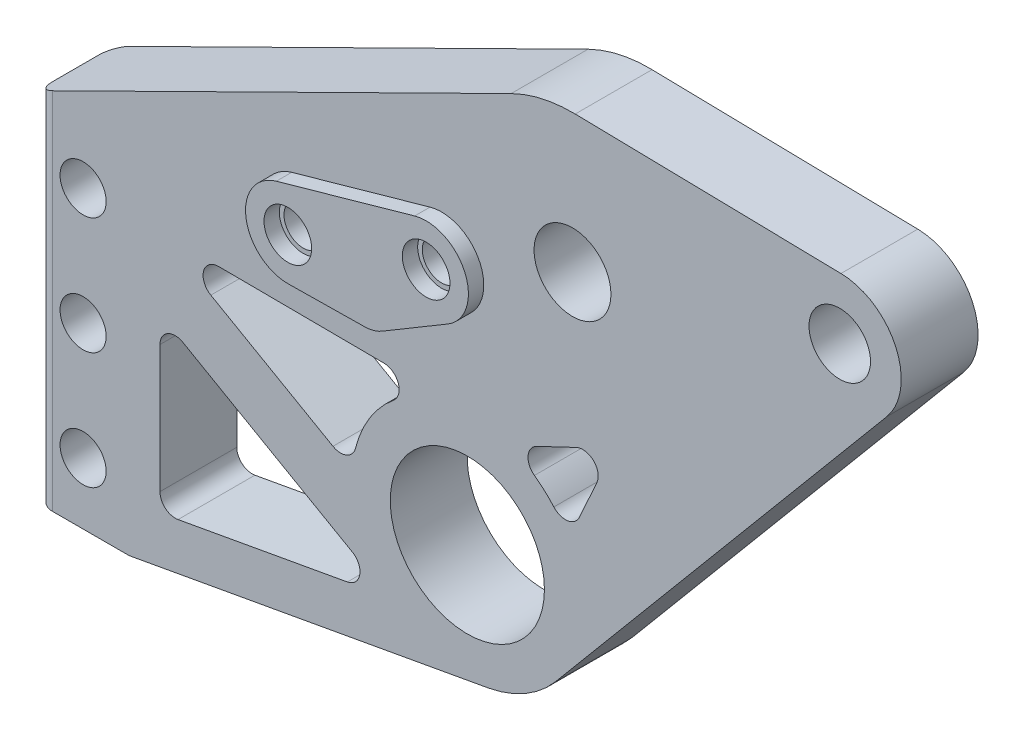
SolidWorks part; units mm, degrees
ref_plane "前视基准面" through (0, 0, 0) normal (0, 0, 1) x (1, 0, 0)
ref_plane "上视基准面" through (0, 0, 0) normal (0, 1, 0) x (1, 0, 0)
ref_plane "右视基准面" through (0, 0, 0) normal (1, 0, 0) x (0, 0, -1)
sketch "草图1" plane through (0, 0, 0) normal (0, 0, 1) x (1, 0, 0)
  line L0 (0, 0) -> (0, 23.2)
  line L1 (3, 11.6) -> (28, 11.6) construction
  line L2 (3, 11.6) -> (0, 11.6) construction
  line L3 (3, 19.2) -> (3, 4) construction
  line L4 (0, 0) -> (6, 0)
  line L5 (28, 11.6) -> (34.8404, 30.3939) construction
  line L6 (28, 11.6) -> (22.2988, 23.804) construction
  line L7 (0, 23.2) -> (30.8499, 38.4608)
  line L8 (6, 0) -> (29.3346, 4.2197)
  line L9 (34.8355, 8.5135) -> (43.043, 26.69)
  line L10 (22.2988, 23.804) -> (21.818, 25.5074) construction
  line L11 (17.3188, 24.2376) -> (26.3173, 26.7773) construction
  circle A0 centre (3, 19.2) radius 1.5
  circle A1 centre (3, 11.6) radius 1.5
  circle A2 centre (3, 4) radius 1.5
  circle A3 centre (28, 11.6) radius 5.015
  circle A4 centre (34.8404, 30.3939) radius 2.5
  arc A5 (43.043, 26.69) -> (30.8499, 38.4608) centre (34.8404, 30.3939) ccw
  circle A6 centre (22.2988, 23.804) radius 1.515
  arc A7 (29.3346, 4.2197) -> (34.8355, 8.5135) centre (28, 11.6) ccw
  circle A8 centre (17.3188, 24.2376) radius 1.25
  circle A9 centre (26.3173, 26.7773) radius 1.25
  point P26 (21.818, 25.5074)
  dimension "D2" = 25
  dimension "D3" = 3
  dimension "D4" = 7.6
  dimension "D6" = 4
  dimension "D7" = 10.03
  dimension "D10" = 5
  dimension "D11" = 18
  dimension "D14" = 3.03
  dimension "D15" = 15
  dimension "D18" = 2.5
  dimension "D1" = 3
  dimension "D5" = 6
  dimension "D8" = 70
  dimension "D9" = 20
  dimension "D12" = 64.96
  dimension "D13" = 13.47
  dimension "D16" = 1.77
  dimension "D17" = 9.35
  dimension "D19" = 15.761
extrude "凸台-拉伸1" add sketch "草图1" along normal blind 5
fillet "圆角1" radius 1 2 edges at (0, 11.6, 0) (0, 11.6, 5)
sketch "草图2" plane through (0, 0, 5) normal (0, 0, 1) x (1, 0, 0)
  line L0 (16.5719, 26.8842) -> (25.5703, 29.4239)
  line L1 (17.3561, 21.4879) -> (22.3293, 21.5553)
  line L2 (23.4484, 21.8712) -> (27.7231, 24.4137)
  arc A0 (16.5719, 26.8842) -> (17.3561, 21.4879) centre (17.3188, 24.2376) ccw
  arc A1 (27.7231, 24.4137) -> (25.5703, 29.4239) centre (26.3173, 26.7773) ccw
  arc A2 (22.3293, 21.5553) -> (23.4484, 21.8712) centre (22.2988, 23.804) ccw
  circle A3 centre (17.3188, 24.2376) radius 1.55
  circle A4 centre (26.3173, 26.7773) radius 1.55
  dimension "D1" = 5.5
  dimension "D2" = 3.1
  dimension "D3" = 3.1
extrude "凸台-拉伸2" add sketch "草图2" along normal blind 1 separate body
sketch "草图3" plane through (0, 0, 5) normal (0, 0, 1) x (1, 0, 0)
  line L0 (6, 0) -> (6, 26.1681) construction
  line L1 (30.8499, 38.4608) -> (1, 23.6947) construction
  line L2 (8, 0.3617) -> (8, 27.1574) construction
  line L3 (37.5481, 21.8108) -> (34.5705, 15.2165)
  line L4 (6, 0) -> (29.3346, 4.2197) construction
  line L5 (8, 3.4103) -> (22.8965, 6.1041)
  line L6 (8, 14.6181) -> (22.8965, 6.1041)
  line L7 (8, 14.6181) -> (8, 3.4103)
  line L8 (8, 19.2253) -> (20.5149, 12.0726)
  line L9 (8, 19.2253) -> (28.0469, 19.0999)
  line L10 (34.8355, 8.5135) -> (43.043, 26.69) construction
  line L11 (30.749, 18.578) -> (37.5481, 21.8108)
  line L12 (26.1673, 32.7974) -> (18.6487, 16.1466) construction
  line L13 (18.6487, 16.1466) -> (31.2532, 22.1396) construction
  circle A0 centre (28, 11.6) radius 7.5 construction
  arc A1 (20.5149, 12.0726) -> (28.0469, 19.0999) centre (28, 11.6) cw
  circle A2 centre (34.8404, 30.3939) radius 9 construction
  arc A3 (34.5705, 15.2165) -> (30.749, 18.578) centre (28, 11.6) ccw
  arc A4 (26.1673, 32.7974) -> (31.2532, 22.1396) centre (34.8404, 30.3939) ccw construction
  dimension "D1" = 15
  dimension "D6" = 18
  dimension "D2" = 2
  dimension "D3" = 3
  dimension "D4" = 40
  dimension "D5" = 4
  dimension "D7" = 3
  dimension "D8" = 3
  dimension "D9" = 3
extrude "切除-拉伸1" cut sketch "草图3" against normal blind 10 contours A3 L3 L11 | L8 A1 L9 | L6 L7 L5 | A4 L12 L13
fillet "圆角2" radius 1 9 edges at (22.8965, 6.1041, 2.5) (8, 3.4103, 2.5) (30.749, 18.578, 2.5) (37.5481, 21.8108, 2.5) (34.5705, 15.2165, 2.5) (8, 14.6181, 2.5) (28.0469, 19.0999, 2.5) (20.5149, 12.0726, 2.5) (8, 19.2253, 2.5)
sketch "草图4" plane through (0, 0, 5) normal (0, 0, 1) x (1, 0, 0)
  line L0 (35.0175, 39.3921) -> (52.3058, 39.0518)
  line L1 (55.2925, 32.4829) -> (33.7476, 6.7818)
  line L2 (34.8404, 30.3939) -> (52.2271, 35.0526) construction
  line L3 (1, 0) -> (6, 0) construction
  circle A0 centre (52.2271, 35.0526) radius 2
  circle A1 centre (34.8404, 30.3939) radius 2.5 construction
  arc A2 (55.2925, 32.4829) -> (52.3058, 39.0518) centre (52.2271, 35.0526) ccw
  arc A3 (43.043, 26.69) -> (30.8499, 38.4608) centre (34.8404, 30.3939) ccw construction
  arc A4 (29.3346, 4.2197) -> (34.8355, 8.5135) centre (28, 11.6) ccw construction
  dimension "D1" = 18
  dimension "D2" = 4
  dimension "D3" = 8
  dimension "D4" = 15
extrude "凸台-拉伸3" add sketch "草图4" against normal blind 5
sketch "草图5" plane through (0, 0, 0) normal (0, 0, -1) x (-1, 0, 0)
  circle A0 centre (-52.2271, 35.0526) radius 4
  circle A1 centre (-52.2271, 35.0526) radius 2
  dimension "D1" = 4
  dimension "D2" = 8
extrude "凸台-拉伸4" [suppressed] add sketch "草图5" along normal blind 44 separate body
